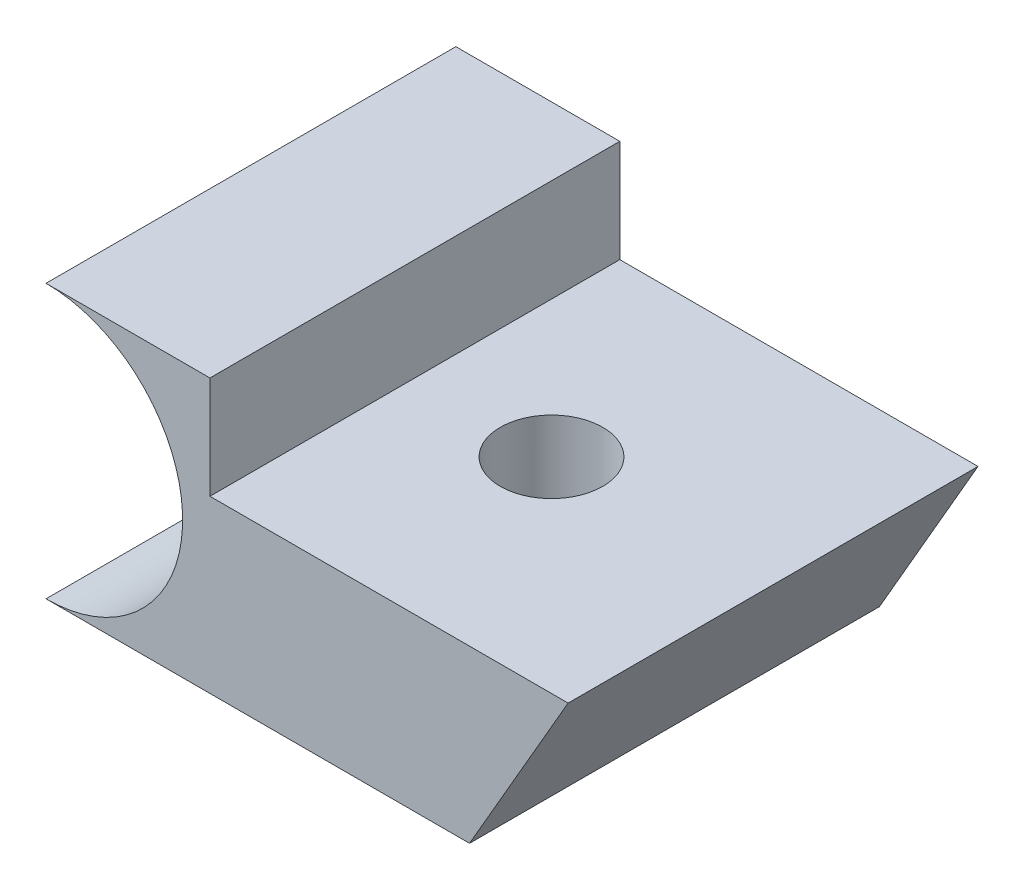
SolidWorks part; units mm, degrees
material "Plain Carbon Steel"
ref_plane "Front Plane" through (0, 0, 0) normal (0, 0, 1) x (1, 0, 0)
ref_plane "Top Plane" through (0, 0, 0) normal (0, 1, 0) x (1, 0, 0)
ref_plane "Right Plane" through (0, 0, 0) normal (1, 0, 0) x (0, 0, -1)
sketch "Sketch1" plane through (0, 0, 0) normal (0, 0, 1) x (1, 0, 0)
  line L1 (0, 0) -> (50.8, 0)
  line L3 (0, 25.4) -> (15.24, 25.4)
  line L4 (50.8, 0) -> (50.8, 15.875)
  line L6 (15.24, 25.4) -> (15.24, 15.875)
  line L7 (15.24, 15.875) -> (50.8, 15.875)
  arc A1 (0, 0) -> (0, 25.4) centre (0, 12.7) ccw
  dimension "D2" = 25.4
  dimension "D1" = 50.8
  dimension "D3" = 9.525
  dimension "D4" = 15.24
extrude "Boss-Extrude1" add sketch "Sketch1" along normal blind 38.1
chamfer "Chamfer1" distance 11.43 angle 60 1 edges at (50.8, 0, 19.05) first distance on face at (25.4, 0, 19.05)
hole_wizard "3/8 (0.375) Diameter Hole1" positions "Sketch5" profile "Sketch3" hole size "3/8" standard "ANSI Inch" end condition through all
sketch "Sketch5" plane through (0, 25.4, 0) normal (0, 1, 0) x (1, 0, 0)
  line L1 (48.5354, -38.1) -> (48.5354, 0) construction
  point P0 (27.94, -19.05)
  dimension "D1" = 20.5954
sketch "Sketch3" plane through (27.94, 25.4, 19.05) normal (1, 0, 0) x (0, 0, 1)
  line L0 (0, 0) -> (0, 25.4)
  line L1 (0, 25.4) -> (4.7625, 25.4)
  line L2 (4.7625, 25.4) -> (4.7625, 0)
  line L5 (4.7625, 0) -> (0, 0)
  line L11 (0, -6.35) -> (0, 107.95) construction
  dimension "Thru Hole Dia." = 9.525
  dimension "Thru Hole Depth" = 25.4
